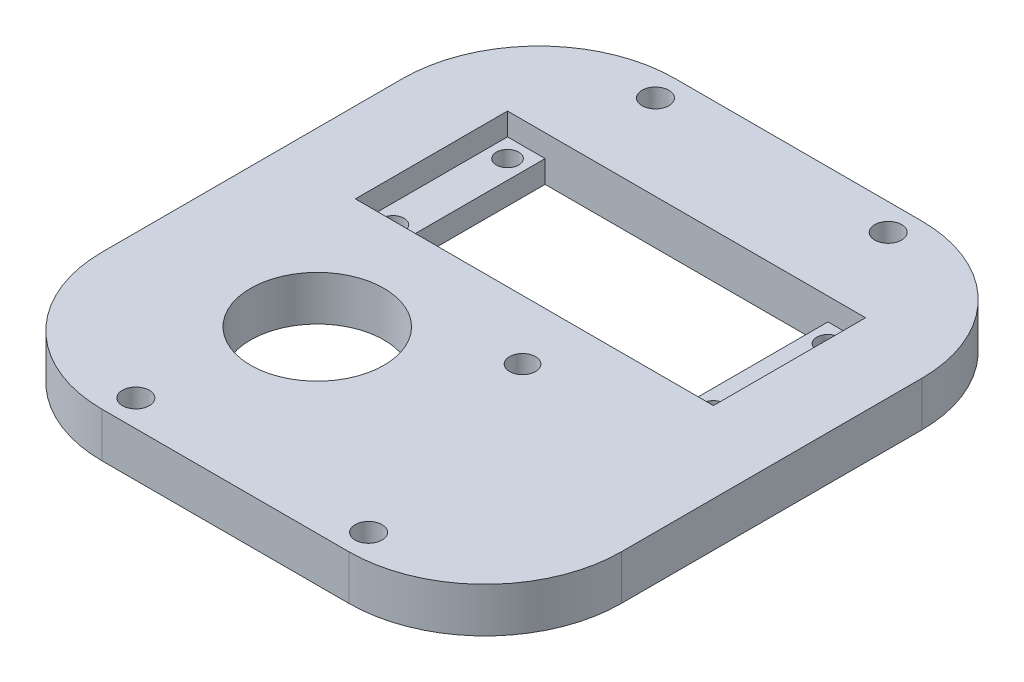
SolidWorks part; units mm, degrees
ref_plane "Front Plane" through (0, 0, 0) normal (0, 0, 1) x (1, 0, 0)
ref_plane "Top Plane" through (0, 0, 0) normal (0, 1, 0) x (1, 0, 0)
ref_plane "Right Plane" through (0, 0, 0) normal (1, 0, 0) x (0, 0, -1)
sketch "Sketch1" plane through (0, 0, 0) normal (0, 1, 0) x (1, 0, 0)
  line L0 (0, 0) -> (5.3232, -16.1451) construction
  line L1 (5.3232, -16.1451) -> (-9.7532, -24) construction
  line L2 (-9.7532, -24) -> (0, 0) construction
  line L3 (-29, -28.7775) -> (-29, 4.7775)
  line L4 (29, -28.7775) -> (29, 4.7775)
  line L5 (-13.7775, -44) -> (13.7775, -44)
  line L6 (-13.7775, 20) -> (13.7775, 20)
  line L7 (0, 0) -> (0, -69.1065) construction
  circle A2 centre (0, 0) radius 6.5 construction
  circle A4 centre (-9.7532, -24) radius 12 construction
  circle A5 centre (5.3232, -16.1451) radius 12 construction
  circle A6 centre (5.3232, -16.1451) radius 6.5 construction
  circle A7 centre (-9.7532, -24) radius 3.2
  circle A13 centre (0, 0) radius 5
  circle A15 centre (5.3232, -16.1451) radius 5.5
  circle A16 centre (-9.7532, -24) radius 5
  circle A17 centre (-9.7532, -24) radius 8
  circle A18 centre (0, 0) radius 18 construction
  arc A23 (-29, 4.7775) -> (-13.7775, 20) centre (-13.7775, 4.7775) cw
  arc A24 (13.7775, 20) -> (29, 4.7775) centre (13.7775, 4.7775) cw
  arc A25 (-29, -28.7775) -> (-13.7775, -44) centre (-13.7775, -28.7775) ccw
  arc A26 (13.7775, -44) -> (29, -28.7775) centre (13.7775, -28.7775) ccw
  circle A28 centre (5.3232, -16.1451) radius 1.45
  circle A29 centre (-9.7532, -24) radius 2
  point P1 (-7.2248, -16.4864)
  point P10 (-4.8766, -12)
  point P13 (-9.7532, -20.8)
  point P15 (-9.7532, -36)
  point P27 (0, 18)
  point P31 (0, -44)
  point P33 (-29, -12)
  point P43 (0, 20)
  dimension "D2" = 17
  dimension "D3" = 13
  dimension "D4" = 17
  dimension "D5" = 6.4
  dimension "D6" = 24
  dimension "D9" = 58
  dimension "D10" = 64
  dimension "D11" = 11
  dimension "D12" = 2.9
  dimension "D13" = 3
  dimension "D7" = 36
  dimension "D15" = 4
  dimension "D8" = 5
  dimension "D14" = 2
extrude "Boss-Extrude1" add sketch "Sketch1" along normal blind 5 contours L5 A26 L4 A24 L6 A23 L3 A25 A13 A15 A17 | A15 | A17 A16 | A16 A7 | A7 A29 | A13 region at (0.4636, 0, 11.406) region at (-12.8627, 0, 24) region at (0, 0, 0) region at (-0.0212, 0, 16.1451) region at (-14.6118, 0, 24) region at (-17.527, 0, 24)
sketch "Sketch4" plane through (0, 5, 0) normal (0, 1, 0) x (1, 0, 0)
  line L0 (-13.7775, 20) -> (13.7775, 20) construction
  line L2 (-13, 17.0248) -> (13, 17.0248) construction
  line L3 (-4.8766, -12) -> (49.0411, -12) construction
  line L4 (-13, -41.0248) -> (13, -41.0248) construction
  line L5 (0, -38.0496) -> (0, -44) construction
  circle A0 centre (13, 17.0248) radius 1.5
  circle A1 centre (-13, 17.0248) radius 1.5
  circle A2 centre (-13, -41.0248) radius 1.5
  circle A3 centre (13, -41.0248) radius 1.5
  point P8 (0, 17.0248)
  point P19 (0, -41.0248)
  dimension "D1" = 3
  dimension "D2" = 26
  dimension "D3" = 2.9752
extrude "Cut-Extrude2" cut sketch "Sketch4" against normal up to surface (5 mm away) up to face at (0, 0, 12)
sketch "Sketch5" plane through (0, 0, 0) normal (0, 1, 0) x (1, 0, 0)
  circle A0 centre (-9.7532, -24) radius 7.45
  dimension "D1" = 14.9
extrude "Boss-Extrude2" [suppressed] add sketch "Sketch5" along normal blind 5.5
extrude "Cut-Extrude6" cut sketch "Sketch5<4>" along normal up to surface (5 mm away) contours A0 region at (-9.7532, 0, 24) up to face at (13, 5, 39.5248)
sketch "Sketch5<4>" plane through (0, 0, 0) normal (0, 1, 0) x (1, 0, 0) same geometry as "Sketch5"
sketch "Sketch6" plane through (0, 5, 0) normal (0, 1, 0) x (1, 0, 0)
  line L0 (-20, 3.3) -> (-15.8, 3.3)
  line L1 (-20, -9.5) -> (20, -9.5)
  line L2 (-20, -9.5) -> (-20, 7.5)
  line L3 (-20, 7.5) -> (20, 7.5)
  line L4 (20, -9.5) -> (20, 7.5)
  line L5 (-20, -9.5) -> (20, 7.5) construction
  line L6 (-20, 7.5) -> (20, -9.5) construction
  line L7 (-15.8, 3.3) -> (-15.8, 7.5)
  line L14 (-20, 7.5) -> (-15.8, 3.3) construction
  line L15 (0, -1) -> (32.0486, -1) construction
  line L16 (0, -1) -> (0, 17.2841) construction
  line L17 (-15.8, 3.3) -> (-20, 3.3)
  line L18 (-15.8, 7.5) -> (-15.8, 3.3)
  line L19 (-20, 3.3) -> (-15.8, 3.3)
  line L20 (-15.8, 3.3) -> (-15.8, 7.5)
  line L21 (-15.8, 3.3) -> (-20, 3.3)
  line L22 (-15.8, 7.5) -> (-15.8, 3.3)
  line L23 (-20, 3.3) -> (-15.8, 3.3)
  line L24 (-15.8, 3.3) -> (-15.8, 7.5)
  line L25 (-15.8, 3.3) -> (-20, 3.3)
  line L26 (-15.8, 7.5) -> (-15.8, 3.3)
  line L27 (-20, 3.3) -> (-15.8, 3.3)
  line L28 (-15.8, 3.3) -> (-15.8, 7.5)
  line L29 (-15.8, 3.3) -> (-20, 3.3)
  line L30 (-15.8, 7.5) -> (-15.8, 3.3)
  line L31 (-20, -5.3) -> (-15.8, -5.3)
  line L32 (-15.8, -5.3) -> (-15.8, -9.5)
  line L33 (20, 3.3) -> (15.8, 3.3)
  line L34 (15.8, 3.3) -> (15.8, 7.5)
  line L35 (20, -5.3) -> (15.8, -5.3)
  line L36 (15.8, -5.3) -> (15.8, -9.5)
  line L37 (-15.8, 3.3) -> (-15.8, -5.3)
  line L38 (15.8, 3.3) -> (15.8, -5.3)
  circle A4 centre (-17.9, 5.4) radius 1.25
  circle A5 centre (-17.9, -7.4) radius 1.25
  circle A6 centre (17.9, 5.4) radius 1.25
  circle A7 centre (17.9, -7.4) radius 1.25
  point P0 (0, -1)
  point P29 (0, 0)
  point P30 (0.5646, -2.8266)
  dimension "D3" = 2.5
  dimension "D1" = 40
  dimension "D2" = 17
  dimension "D4" = 4.2
  dimension "D5" = 1
extrude "Cut-Extrude8" cut sketch "Sketch6" against normal up to surface (5 mm away) contours L36 L35 L4 L33 L34 L3 L7 L0 L2 L31 L32 L1 | A6 | A7 | A5 | A4 region at (0, 5, 1) region at (-17.9, 5, -5.4) region at (-17.9, 5, 7.4) region at (17.9, 5, -5.4) region at (17.9, 5, 7.4) up to face at (-9.7532, 0, 31.45)
extrude "Cut-Extrude9" cut sketch "Sketch6<4>" against normal offset from surface (2.5 mm away) 2.5 contours L0 L7 L3 L2 A4 | L34 L33 L4 L3 A6 | L32 L31 L2 L1 A5 | L35 L36 L1 L4 A7 | L37 L0 L2 L31 | L33 L38 L35 L4 region at (-19.9406, 5, -5.4) region at (-17.9, 5, 1) region at (-17.9, 5, 5.3594) region at (17.9, 5, -7.4406) region at (17.9, 5, 1) region at (15.8594, 5, 7.4) up to face at (-17.9, 0, -4.15)
sketch "Sketch6<4>" plane through (0, 5, 0) normal (0, 1, 0) x (1, 0, 0) same geometry as "Sketch6"
